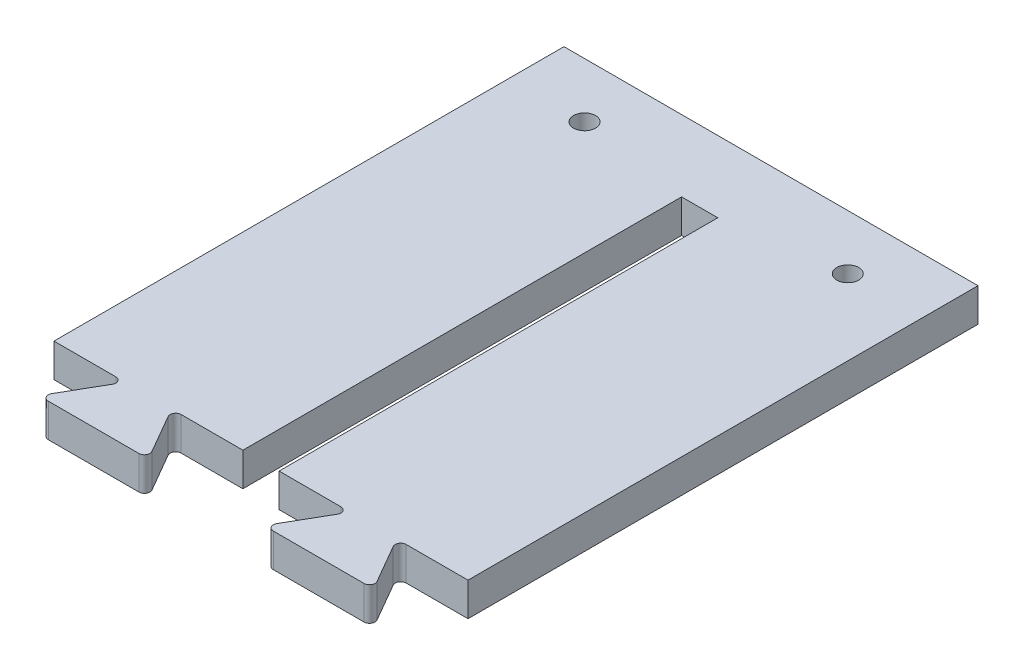
SolidWorks part; units mm, degrees
ref_plane "Front Plane" through (0, 0, 0) normal (0, 0, 1) x (1, 0, 0)
ref_plane "Top Plane" through (0, 0, 0) normal (0, 1, 0) x (1, 0, 0)
ref_plane "Right Plane" through (0, 0, 0) normal (1, 0, 0) x (0, 0, -1)
sketch "Sketch1" plane through (0, 0, 0) normal (0, 1, 0) x (1, 0, 0)
  line L0 (-19.375, 0) -> (-19.375, 46.5)
  line L1 (-19.375, 46.5) -> (19.375, 46.5)
  line L2 (19.375, 46.5) -> (19.375, 0)
  line L3 (19.375, 0) -> (12.375, 0)
  line L4 (12.375, 0) -> (15.2618, -5)
  line L5 (15.2618, -5) -> (5.2618, -5)
  line L6 (5.2618, -5) -> (8.1485, 0)
  line L7 (8.1485, 0) -> (-8.1485, 0)
  line L8 (-8.1485, 0) -> (-5.2618, -5)
  line L9 (-5.2618, -5) -> (-15.2618, -5)
  line L10 (-15.2618, -5) -> (-12.375, 0)
  line L11 (-12.375, 0) -> (-19.375, 0)
  point P13 (0, 0)
  dimension "D1" = 46.5
  dimension "D2" = 38.75
  dimension "D3" = 10
  dimension "D4" = 10
  dimension "D5" = 60
  dimension "D6" = 60
  dimension "D7" = 7
  dimension "D8" = 7
  dimension "D9" = 5
  dimension "D10" = 5
extrude "Boss-Extrude1" add sketch "Sketch1" along normal blind 3.05
fillet "Fillet1" radius 0.5 8 edges at (12.375, 1.525, 0) (15.2618, 1.525, 5) (5.2618, 1.525, 5) (8.1485, 1.525, 0) (-8.1485, 1.525, 0) (-5.2618, 1.525, 5) (-15.2618, 1.525, 5) (-12.375, 1.525, 0)
sketch "Sketch3" plane through (0, 3.05, 0) normal (0, 1, 0) x (1, 0, 0)
  line L0 (0, 40) -> (0, 0) construction
  line L2 (19.375, 46.5) -> (-19.375, 46.5) construction
  line L3 (-1.65, 40) -> (1.65, 40)
  line L4 (-1.65, 40) -> (-1.65, 0)
  line L5 (-1.65, 0) -> (1.65, 0)
  line L6 (1.65, 40) -> (1.65, 0)
  line L8 (-1.65, -1.2) -> (1.65, -1.2)
  line L9 (-1.65, -1.2) -> (-1.65, -2.2)
  line L10 (-1.65, -2.2) -> (1.65, -2.2)
  line L11 (1.65, -1.2) -> (1.65, -2.2)
  point P8 (0, 40)
  point P15 (0, -1.2)
  dimension "D1" = 3.3
  dimension "D2" = 40
  dimension "D3" = 6.5
  dimension "D4" = 1.2
  dimension "D5" = 1
extrude "Cut-Extrude2" cut sketch "Sketch3" against normal through all
sketch "Sketch8" plane through (0, 3.05, 0) normal (0, 1, 0) x (1, 0, 0)
  line L0 (0, 0) -> (0, 40) construction
  line L1 (-11.2618, 37) -> (-9.2618, 37)
  line L2 (-11.2618, 37) -> (-11.2618, 3)
  line L3 (-11.2618, 3) -> (-9.2618, 3)
  line L4 (-9.2618, 37) -> (-9.2618, 3)
  line L5 (-19.375, 0) -> (-13.241, 0) construction
  line L6 (-14.3957, -5) -> (-6.1278, -5) construction
  line L8 (11.2618, 3) -> (9.2618, 3)
  line L9 (9.2618, 37) -> (9.2618, 3)
  line L10 (11.2618, 37) -> (9.2618, 37)
  line L11 (11.2618, 37) -> (11.2618, 3)
  line L12 (1.65, 40) -> (-1.65, 40) construction
  point P5 (-10.2618, -5)
  point P10 (-10.2618, 3)
  dimension "D1" = 2
  dimension "D2" = 3
  dimension "D3" = 3
extrude "Cut-Extrude3" [suppressed] cut sketch "Sketch8" against normal through all
fillet "Fillet2" [suppressed] radius 0.5
sketch "Damper Hole Locations" plane through (0, 3.05, 0) normal (0, 1, 0) x (1, 0, 0)
  line L0 (0, 40) -> (0, 0) construction
  line L3 (19.375, 46.5) -> (-19.375, 46.5) construction
  circle A0 centre (-12, 41.5) radius 1.5
  circle A1 centre (12, 41.5) radius 1.5
  dimension "D1" = 3
  dimension "D2" = 12
  dimension "D3" = 5
hole_wizard "M3 Tapped Damper Holes" positions "Sketch6" profile "Sketch7" hole size "Ø2.0" standard "ANSI Metric" end condition through all
sketch "Sketch6" plane through (0, 3.05, 0) normal (0, 1, 0) x (1, 0, 0)
  point P0 (-12, 41.5)
  point P3 (12, 41.5)
sketch "Sketch7" plane through (-12, 3.05, -41.5) normal (1, 0, 0) x (0, 0, 1)
  line L0 (0, 0) -> (0, 3.05)
  line L1 (0, 3.05) -> (1, 3.05)
  line L2 (1, 3.05) -> (1, 0)
  line L5 (1, 0) -> (0, 0)
  line L11 (0, -6.35) -> (0, 107.95) construction
  dimension "Thru Hole Dia." = 2
  dimension "Thru Hole Depth" = 3.05
sketch "Sketch9" plane through (0, 3.05, 0) normal (0, 1, 0) x (1, 0, 0)
  line L0 (-19.375, 46.5) -> (-18.875, 46.5)
  line L1 (19.375, 46.5) -> (-19.375, 46.5) construction
  line L2 (-18.875, 46.5) -> (-18.875, 0)
  line L3 (-19.375, 0) -> (-13.241, 0) construction
  line L4 (-18.875, 0) -> (-19.375, 0)
  line L5 (-19.375, 0) -> (-19.375, 46.5)
  line L6 (19.375, 46.5) -> (18.875, 46.5)
  line L7 (18.875, 46.5) -> (18.875, 0)
  line L8 (13.241, 0) -> (19.375, 0) construction
  line L9 (18.875, 0) -> (19.375, 0)
  line L10 (19.375, 0) -> (19.375, 46.5)
  dimension "D1" = 0.5
  dimension "D2" = 0.5
extrude "Cut-Extrude4" cut sketch "Sketch9" against normal through all
